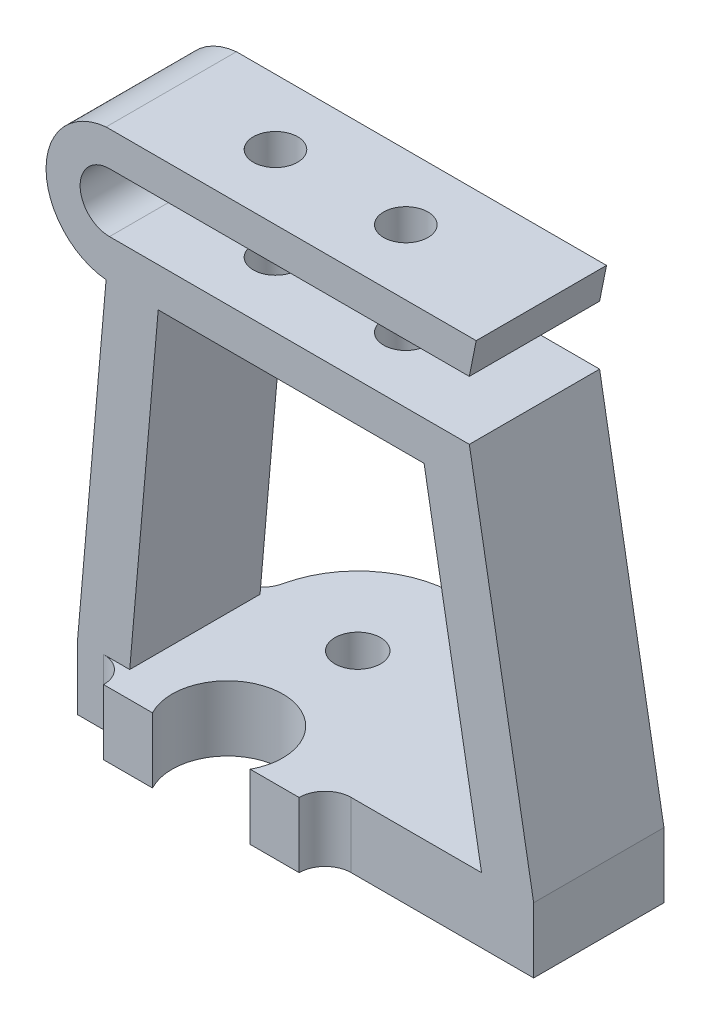
SolidWorks part; units mm, degrees
ref_plane "Front Plane" through (0, 0, 0) normal (0, 0, 1) x (1, 0, 0)
ref_plane "Top Plane" through (0, 0, 0) normal (0, 1, 0) x (1, 0, 0)
ref_plane "Right Plane" through (0, 0, 0) normal (1, 0, 0) x (0, 0, -1)
sketch "Sketch1" plane through (0, 0, 0) normal (0, 1, 0) x (1, 0, 0)
  line L0 (0, 0) -> (0, 20.5292) construction
  line L1 (0, 0) -> (28.1847, 0) construction
  line L2 (0, -10) -> (0, 10) construction
  line L3 (-7.5, -10) -> (-7.5, 10)
  line L4 (7.5, -10) -> (7.5, 10)
  circle A0 centre (0, 0) radius 4.25
  circle A1 centre (0, 10) radius 1.75
  circle A2 centre (0, -10) radius 1.75
  arc A3 (-7.5, -10) -> (7.5, -10) centre (0, -10) ccw
  arc A4 (7.5, 10) -> (-7.5, 10) centre (0, 10) ccw
  point P7 (0, 0)
  dimension "D1" = 8.5
  dimension "D2" = 3.5
  dimension "D3" = 10
  dimension "D4" = 15
extrude "Boss-Extrude1" add sketch "Sketch1" along normal blind 5
sketch "Sketch2" plane through (7.5, 0, 0) normal (1, 0, 0) x (0, 0, -1)
  line L0 (-10, 0) -> (10, 0) construction
  line L1 (-10, 5) -> (10, 5)
  line L2 (-10, 5) -> (-10, 0)
  line L3 (-10, 0) -> (10, 0)
  line L4 (10, 5) -> (10, 0)
  point P7 (0, 5)
  dimension "D1" = 20
extrude "Boss-Extrude2" add sketch "Sketch2" along normal blind 16
sketch "Sketch3" plane through (0, 0, 10) normal (0, 0, 1) x (1, 0, 0)
  line L0 (7.5, 5) -> (14.2173, 18.4119)
  line L1 (14.2173, 18.4119) -> (19.2173, 18.4119)
  line L2 (23.5, 5) -> (28.9652, 15.9119)
  line L3 (19.2173, 18.4119) -> (45.4641, 18.4119)
  line L4 (45.4641, 18.4119) -> (48.5, 0)
  line L5 (45.0473, 2.5) -> (42.8358, 15.9119)
  line L6 (42.8358, 15.9119) -> (28.9652, 15.9119)
  line L7 (23.5, 2.5) -> (45.0473, 2.5)
  line L8 (23.5, 5) -> (23.5, 0) construction
  line L9 (23.5, 0) -> (48.5, 0)
  line L10 (23.5, 5) -> (7.5, 5)
  line L11 (23.5, 2.5) -> (23.5, 0)
  dimension "D1" = 15
  dimension "D2" = 2.5
  dimension "D3" = 2.5
  dimension "D4" = 3
  dimension "D5" = 25
extrude "Boss-Extrude3" [suppressed] add sketch "Sketch3" against normal up to surface (12.5 mm away)
extrude "Boss-Extrude4" add sketch "Sketch2<2>" against normal blind 4 from surface starting at face at (-7.5, 2.5, 0)
sketch "Sketch2<2>" plane through (7.5, 0, 0) normal (1, 0, 0) x (0, 0, -1) same geometry as "Sketch2"
sketch "Sketch4" plane through (0, 0, 10) normal (0, 0, 1) x (1, 0, 0)
  line L0 (-11.5, 5) -> (-7.5, 5)
  line L1 (-11.5, 5) -> (6.7958, 5)
  line L2 (-7.5, 5) -> (10.7958, 5)
  line L3 (6.7958, 5) -> (10.7958, 5)
  line L4 (19.5, 5) -> (23.5, 5)
  line L5 (19.5, 5) -> (15.0918, 30)
  line L6 (23.5, 5) -> (19.0918, 30)
  line L7 (15.0918, 30) -> (19.0918, 30)
  line L8 (-11.5, 5) -> (-7.5, 5)
  line L9 (-11.5, 5) -> (-9.3128, 30)
  line L10 (-7.5, 5) -> (-5.3128, 30)
  line L11 (-9.3128, 30) -> (-5.3128, 30)
  line L12 (23.5, 5) -> (7.5, 5) construction
  line M2 (-7.5, 5) -> (-11.5, 5)
  dimension "D1" = 85
  dimension "D2" = 25
  dimension "D3" = 4
  dimension "D4" = 100
  dimension "D5" = 25
extrude "Boss-Extrude5" add sketch "Sketch4" against normal up to surface (20 mm away) contours L11 L9 L10 M2 | L7 L5 L3 L4 L6 region at (-8.4064, 17.5, 10) region at (19.2959, 17.5, 10) up to face at (-9.5, 2.5, -10)
sketch "Sketch5" plane through (0, 0, 10) normal (0, 0, 1) x (1, 0, 0)
  line L0 (19.0918, 30) -> (-9.3128, 30)
  line L1 (19.0918, 30) -> (18.5628, 33)
  line L2 (23.5, 5) -> (19.0918, 30) construction
  line L3 (18.5628, 33) -> (-9.0503, 33)
  line L4 (-9.3128, 30) -> (-8.2879, 41.7144) construction
  line L5 (-11.5, 5) -> (-9.3128, 30) construction
  line L6 (-9.0503, 37.5134) -> (18.5628, 37.5134)
  line L7 (-9.3128, 40.1576) -> (19.0918, 40.1576)
  line L8 (19.0918, 40.1576) -> (18.5628, 37.5134)
  arc A0 (-9.0503, 37.5134) -> (-9.0503, 33) centre (-9.0503, 35.2567) ccw
  arc A1 (-9.3128, 40.1576) -> (-9.3128, 30) centre (-8.8183, 35.0788) ccw
  dimension "D1" = 3
  dimension "D2" = 4.5134
extrude "Boss-Extrude6" add sketch "Sketch5" against normal up to surface (20 mm away) up to face at (16.5262, 10.7143, -10)
sketch "Sketch7" plane through (0, 0, 10) normal (0, 0, 1) x (1, 0, 0)
  line L0 (-7.5, 5) -> (-7.5, 0)
  line L1 (-7.5, 0) -> (-22.1398, 0)
  line L2 (-22.1398, 0) -> (-22.1398, 42.5159)
  line L3 (-22.1398, 42.5159) -> (27.2836, 42.5159)
  line L4 (27.2836, 42.5159) -> (27.2836, 0)
  line L5 (27.2836, 0) -> (7.5, 0)
  line L6 (7.5, 0) -> (7.5, 5)
  line L7 (7.5, 5) -> (-7.5, 5) construction
  line L8 (7.5, 5) -> (-7.5, 5)
extrude "Cut-Extrude1" cut sketch "Sketch7" against normal blind 10
fillet "Fillet1" radius 2 4 edges at (7.5, 2.5, -10) (-7.5, 2.5, -10) (7.5, 2.5, 0) (-7.5, 2.5, 0)
sketch "Sketch8" plane through (0, 5, 0) normal (0, 1, 0) x (1, 0, 0)
  line L0 (-9.3128, 0) -> (19.0918, 0) construction
  line L1 (-16.5467, -2) -> (15.1171, -2)
  line L2 (-16.5467, -2) -> (-16.5467, -19.3176)
  line L3 (-16.5467, -19.3176) -> (15.1171, -19.3176)
  line L4 (15.1171, -2) -> (15.1171, -19.3176)
  dimension "D1" = 2
extrude "Cut-Extrude2" cut sketch "Sketch8" against normal through all
sketch "Sketch9" plane through (0, 40.1576, 0) normal (0, 1, 0) x (1, 0, 0)
  line L0 (-9.3128, 5) -> (19.0918, 5) construction
  line L1 (-9.3128, 10) -> (-9.3128, 0) construction
  line L2 (19.0918, 10) -> (19.0918, 0) construction
  circle A0 centre (-1.3128, 5) radius 1.7
  circle A1 centre (8.6872, 5) radius 1.7
  dimension "D1" = 3.4
  dimension "D2" = 3.4
  dimension "D3" = 10
  dimension "D4" = 8
extrude "Cut-Extrude3" cut sketch "Sketch9" against normal up to surface (10.1576 mm away) up to face at (4.8895, 30, -5)
